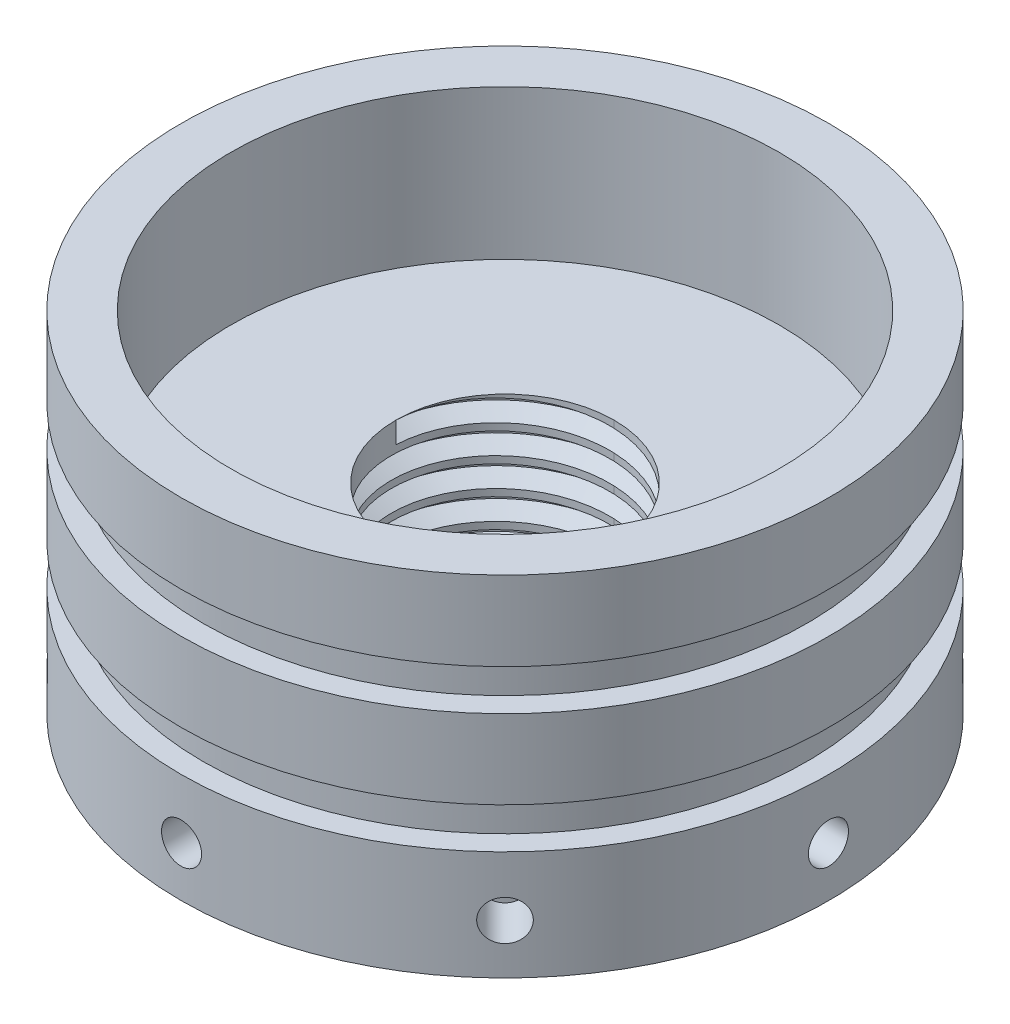
SolidWorks part; units mm, degrees
note: '?' marks a value the reader was unsure of.
material "6061-T6 (SS)"
ref_plane "Front Plane" through (0, 0, 0) normal (0, 0, 1) x (1, 0, 0)
ref_plane "Top Plane" through (0, 0, 0) normal (0, 1, 0) x (1, 0, 0)
ref_plane "Right Plane" through (0, 0, 0) normal (1, 0, 0) x (0, 0, -1)
sketch "Sketch1" plane through (0, 0, 0) normal (0, 0, 1) x (1, 0, 0)
  line L0 (0, 0) -> (0, 25.4) construction
  line L1 (-41.275, -44.45) -> (-41.275, 0)
  line L2 (-20.32, -52.832) -> (-20.32, -31.75)
  line L3 (-8.9065, -52.832) -> (-8.9065, -39.37)
  line L4 (-13.9116, -19.05) -> (-34.925, -19.05)
  line L5 (-34.925, -19.05) -> (-34.925, 0)
  line L6 (-34.925, 0) -> (-41.275, 0)
  line L8 (-8.9065, -52.832) -> (-20.32, -52.832)
  line L9 (55, 0) -> (-55, 0) construction
  line L10 (-41.275, -44.45) -> (-34.925, -44.45)
  line L11 (-20.32, -31.75) -> (-34.925, -31.75)
  line L12 (-34.925, -44.45) -> (-34.925, -31.75)
  line L13 (-13.9116, -39.37) -> (-13.9116, -19.05)
  line L14 (-8.9065, -39.37) -> (-13.9116, -39.37)
  dimension "D6" = 8.9065
  dimension "D7" = 13.462
  dimension "D9" = 12.7
  dimension "D8" = 20.32
  dimension "D2" = 34.925
  dimension "D3" = 44.45
  dimension "D4" = 6.35
  dimension "D5" = 20.32
  dimension "D10" = 13.9116
  dimension "D11" = 12.7
revolve "Revolve1" add sketch "Sketch1" angle 360 about L0
ref_plane "Plane1" through (0, 0, 0) normal (-1, 0, 0) x (0, 0, -1)
ref_plane "Plane2" through (0, 0, 0) normal (-1, 0, 0) x (0, 0, -1)
ref_plane "Plane3" through (0, 0, 0) normal (-1, 0, 0) x (0, 0, -1)
ref_plane "Plane4" through (0, 0, 0) normal (-1, 0, 0) x (0, 0, -1)
ref_plane "Plane5" through (0, 0, 0) normal (-1, 0, 0) x (0, 0, -1)
ref_plane "Plane6" through (0, 0, 0) normal (-1, 0, 0) x (0, 0, -1)
ref_plane "Plane7" through (0, 0, 0) normal (-1, 0, 0) x (0, 0, -1)
ref_plane "Plane8" through (0, 0, 0) normal (-1, 0, 0) x (0, 0, -1)
ref_plane "Plane9" through (0, 0, 0) normal (-1, 0, 0) x (0, 0, -1)
ref_plane "Plane10" through (0, 0, 0) normal (-1, 0, 0) x (0, 0, -1)
ref_plane "Plane11" through (0, 0, 0) normal (-1, 0, 0) x (0, 0, -1)
ref_plane "Plane12" through (0, -38.1, 0) normal (0, -1, 0) x (-1, 0, 0)
ref_axis "Axis1" through (-88.99, -38.1, 0) along (1, 0, 0)?
ref_axis "Axis2" through (0, -65.0537, 0) along (0, 1, 0)
hole_wizard "1/4-20 Tapped Hole1" positions "3DSketch1" profile "Sketch8" tap size "1/4-20" standard "ANSI Inch"
sketch3d "3DSketch1"
  line L0 (-88.99, -38.1, 0) -> (88.99, -38.1, 0) construction
  point P0 (41.275, -38.1, 0)
sketch "Sketch8" plane through (41.275, -38.1, 0) normal (0, 1, 0) x (0, 0, -1)
  line L0 (0, 0) -> (0, 6.35)
  line L1 (0, 6.35) -> (2.5527, 6.35)
  line L2 (2.5527, 6.35) -> (2.5527, 0)
  line L5 (2.5527, 0) -> (0, 0)
  line L11 (0, -6.35) -> (0, 107.95) construction
  dimension "Thru Tap Drill Dia." = 5.1054
  dimension "Thru Tap Drill Depth" = 6.35
cosmetic thread "Hole Thread1" parameters "D2"=6.35
pattern_circular "CirPattern1" count 8 over 360 about axis through (0, -65.0537, 0) along (0, 1, 0) of "1/4-20 Tapped Hole1"
thread "Thread1" pitch 3.6286 start angle 0, offset 0, length 0, pitch 3.6286, diameter 27.8232
ref_plane "Plane13" through (-13.9116, -19.05, 0) normal (0, 0, 1) x (-1, 0, 0)
sketch "Thread Profile1" plane through (-13.9116, -19.05, 0) normal (0, 0, 1) x (-1, 0, 0)
  line L0 (0, 0) -> (0, 3.6286) construction
  line L1 (0, 0) -> (1.964, 1.1339)
  line L2 (1.964, 1.1339) -> (1.964, 1.5875)
  line L3 (1.964, 1.5875) -> (0, 2.7214)
  line L4 (1.964, 1.3607) -> (0, 1.3607) construction
  line L11 (0, 0) -> (0, 2.7214)
  point P2 (0, 0)
  dimension "Pitch" = 3.6286
  dimension "Profile_Angle" = 60
  dimension "Profile_Land" = 0.4536
  dimension "Profile_Height" = 1.964
ref_plane "Plane14" through (0, 0, 0) normal (-1, 0, 0) x (0, 0, -1)
sketch "Sketch10" plane through (0, 0, 0) normal (-1, 0, 0) x (0, 0, -1)
  line L0 (38.4535, 15.2938) -> (41.3618, 15.2938)
  line L1 (41.3618, 15.2938) -> (41.3618, 10.1062)
  line L2 (41.3618, 10.1062) -> (38.4535, 10.1062)
  line L3 (38.4535, 10.1062) -> (38.4535, 15.2938)
  line L4 (0, 50) -> (0, -50) construction
  line L5 (-41.275, 0) -> (41.275, 0) construction
  point P4 (38.4556, 28.8052)
  point P5 (41.3618, 12.7)
  point P6 (38.44, 23.6175)
  point P7 (0, 0)
  point P11 (38.4535, 23.8325)
  dimension "D1" = 5.1877
  dimension "D2" = 90
  dimension "D3" = 90
  dimension "D4" = 2.9083
  dimension "D5" = 12.7
revolve "Groove for AS 568-234, O-Ring1" cut sketch "Sketch10"
pattern_linear "LPattern1" count 2 spacing 15.24 along (0, -1, 0) of "Groove for AS 568-234, O-Ring1"
